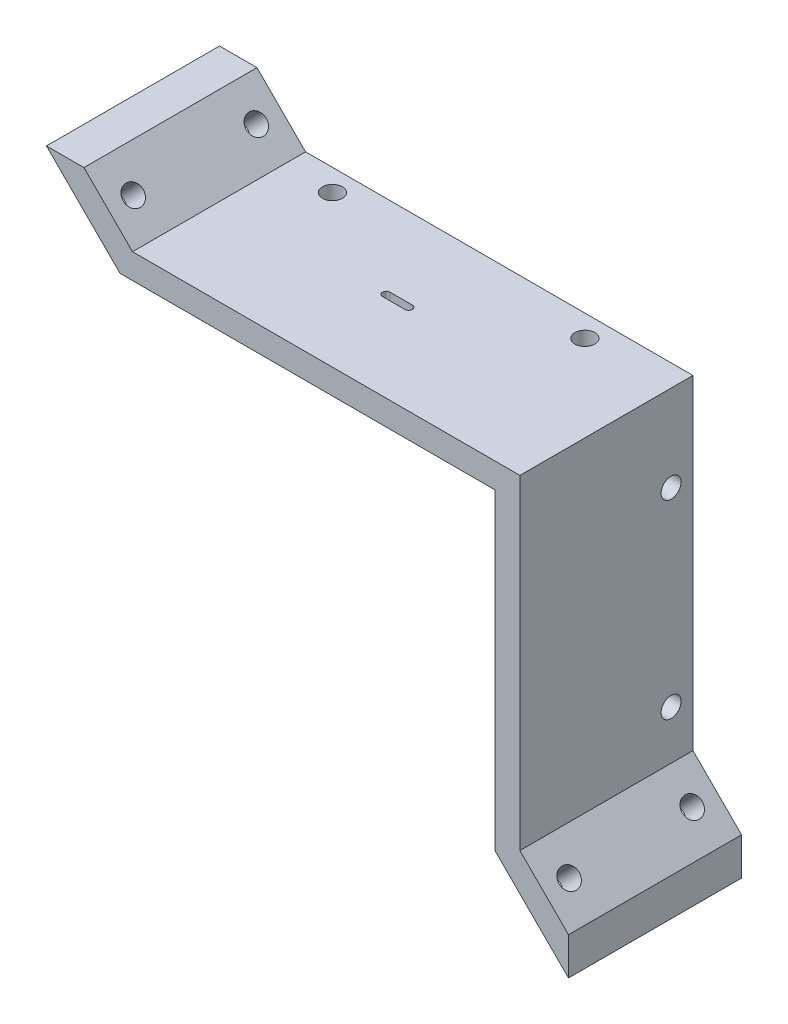
SolidWorks part; units mm, degrees
ref_plane "Front Plane" through (0, 0, 0) normal (0, 0, 1) x (1, 0, 0)
ref_plane "Top Plane" through (0, 0, 0) normal (0, 1, 0) x (1, 0, 0)
ref_plane "Right Plane" through (0, 0, 0) normal (1, 0, 0) x (0, 0, -1)
sketch "Sketch1" plane through (0, 0, 0) normal (0, 0, 1) x (1, 0, 0)
  line L0 (-34, 29) -> (34, 29)
  line L1 (-30, 25) -> (30, 25)
  line L2 (-30, 25) -> (-30, -25) construction
  line L3 (-30, -25) -> (30, -25) construction
  line L4 (30, 25) -> (30, -25)
  line L5 (0, -25) -> (0, 25) construction
  line L6 (-30, 0) -> (30, 0) construction
  line L7 (34, 29) -> (34, -29)
  line L8 (-34, -29) -> (34, -29) construction
  line L9 (-34, 29) -> (-34, -29) construction
  line L10 (-30, 25) -> (-34, 29)
  line L11 (30, -25) -> (34, -29)
  point P0 (0, 0)
  dimension "D1" = 60
  dimension "D2" = 50
  dimension "D3" = 4
extrude "Boss-Extrude1" add sketch "Sketch1" along normal blind 27.7
sketch "Sketch2" plane through (34, 0, 0) normal (1, 0, 0) x (0, 0, -1)
  line L1 (0, -29) -> (0, 29) construction
  circle A0 centre (-3.5, -15.2) radius 1.6
  circle A1 centre (-3.5, 15.2) radius 1.6
  point P6 (0, 0)
  dimension "D1" = 9.8
  dimension "D2" = 3.2
  dimension "D3" = 3.5
  dimension "D4" = 9.8
extrude "Cut-Extrude1" cut sketch "Sketch2" against normal blind 6.4
ref_plane "Plane1" through (2.5, -2.5, 0) normal (-0.7071, 0.7071, 0) x (0.7071, 0.7071, 0)
mirror "Mirror1" about plane through (2.5, -2.5, 0) normal (-0.7071, 0.7071, 0) of face at (34, 15.2, 1.9)
mirror "Mirror2" about plane through (0, 0, 0) normal (1, 0, 0) of face at (20.2, 29, 1.9)
sketch "Sketch3" plane through (0, 0, 27.7) normal (0, 0, 1) x (1, 0, 0)
  line L0 (-34, 29) -> (-41.7782, 36.7782)
  line L1 (-41.7782, 36.7782) -> (-35.7782, 36.7782)
  line L2 (-35.7782, 36.7782) -> (-28, 29)
  line L3 (34, 29) -> (-34, 29) construction
  line L4 (-28, 29) -> (-34, 29)
  line L5 (-34, 29) -> (-30, 25) construction
  line L6 (34, -29) -> (41.7782, -36.7782)
  line L8 (41.7782, -30.7782) -> (34, -23)
  line L9 (34, -29) -> (34, 29) construction
  line L10 (34, -23) -> (34, -29)
  line L11 (41.7782, -36.7782) -> (41.7782, -30.7782)
  line L12 (30, -25) -> (34, -29) construction
  dimension "D1" = 6
  dimension "D2" = 11
extrude "Boss-Extrude2" add sketch "Sketch3" against normal up to surface (27.7 mm away) up to face at (10.6667, 9, 0)
sketch "Sketch4" plane through (0.5, 0.5, 0) normal (0.7071, 0.7071, 0) x (0, 0, -1)
  line L0 (-27.7, 40.3051) -> (-27.7, 51.3051) construction
  line L1 (0, 40.3051) -> (0, 51.3051) construction
  line L2 (-51.0608, 0.0051) -> (29.1449, 0.0051) construction
  line L5 (0, 40.3051) -> (-27.7, 40.3051) construction
  circle A0 centre (-4, 45.8051) radius 1.6
  circle A1 centre (-23.7, 45.8051) radius 1.6
  circle A2 centre (-23.7, -45.7949) radius 1.6
  circle A3 centre (-4, -45.7949) radius 1.6
  point P11 (0, 45.8051)
  dimension "D1" = 3.2
  dimension "D2" = 4
  dimension "D3" = 4
  dimension "D4" = 40.3
extrude "Cut-Extrude2" cut sketch "Sketch4" against normal blind 8 and the other way blind 8
sketch "Sketch5" plane through (0, 25, 0) normal (0, -1, 0) x (1, 0, 0)
  line L0 (-1.8, 13.3) -> (1.8, 13.3) construction
  line L1 (-1.8, 13.9) -> (1.8, 13.9)
  line L2 (-1.8, 12.7) -> (1.8, 12.7)
  line L3 (-30, 27.7) -> (30, 27.7) construction
  arc A0 (-1.8, 13.9) -> (-1.8, 12.7) centre (-1.8, 13.3) ccw
  arc A1 (1.8, 12.7) -> (1.8, 13.9) centre (1.8, 13.3) ccw
  point P2 (0, 13.3)
  point P7 (2.4, 13.3)
  point P8 (-2.4, 13.3)
  point P9 (0, 0)
  dimension "D2" = 4.8
  dimension "D1" = 1.2
  dimension "D3" = 15
extrude "Cut-Extrude3" cut sketch "Sketch5" against normal blind 8
